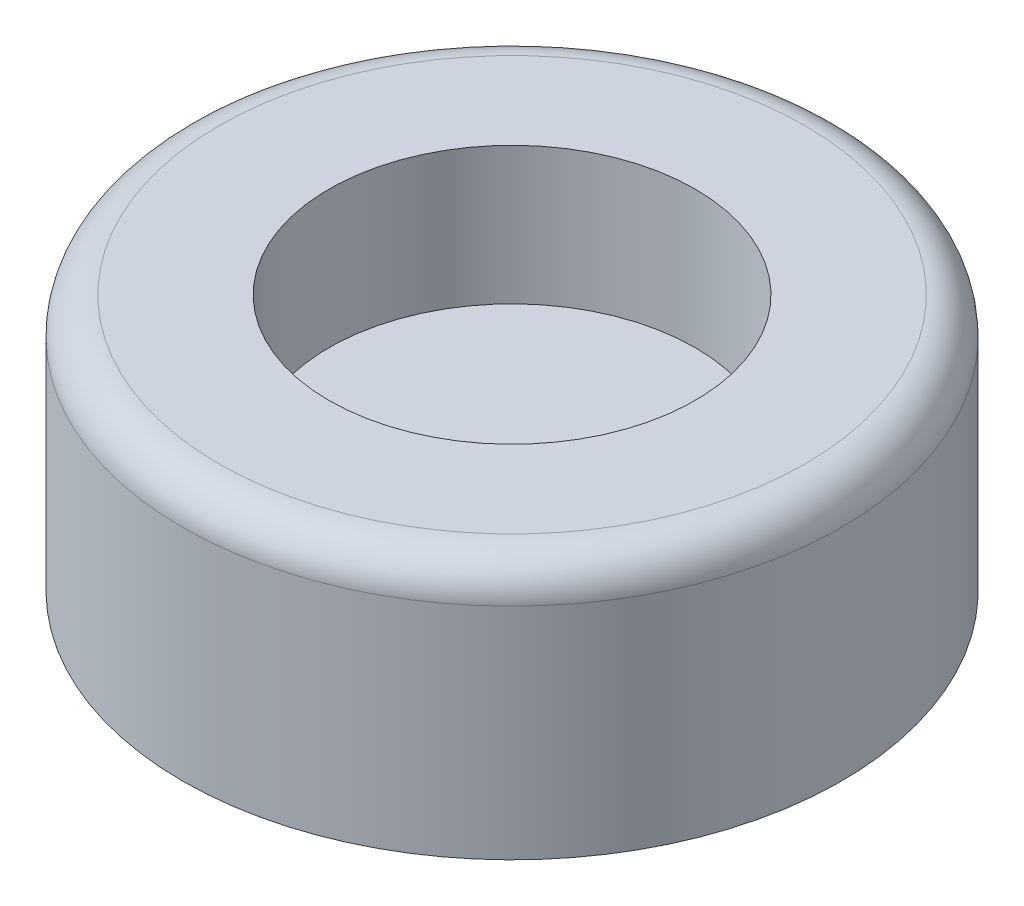
SolidWorks part; units mm, degrees
ref_plane "Front Plane" through (0, 0, 0) normal (0, 0, 1) x (1, 0, 0)
ref_plane "Top Plane" through (0, 0, 0) normal (0, 1, 0) x (1, 0, 0)
ref_plane "Right Plane" through (0, 0, 0) normal (1, 0, 0) x (0, 0, -1)
sketch "Sketch1" plane through (0, 0, 0) normal (0, 1, 0) x (1, 0, 0)
  circle A0 centre (0, 0) radius 11.43
extrude "Boss-Extrude1" add sketch "Sketch1" along normal blind 8.89
sketch "Sketch2" plane through (0, 8.89, 0) normal (0, 1, 0) x (1, 0, 0)
  circle A0 centre (0, 0) radius 6.35
extrude "Cut-Extrude1" cut sketch "Sketch2" against normal blind 4.7625
sketch "Sketch3" plane through (0, 0, 0) normal (0, -1, 0) x (1, 0, 0)
  circle A0 centre (0, 0) radius 3.175
fillet "Fillet4" radius 1.27 1 edges at (0, 8.89, 11.43)
sketch "Sketch4" plane through (0, 8.89, 0) normal (0, 1, 0) x (1, 0, 0)
  line L0 (0, 0) -> (0, 10.16) construction
  circle A0 centre (0, 0) radius 10.16 construction
  circle A1 centre (0, 0) radius 11.938 construction
  circle A2 centre (0, 11.938) radius 1.5875
ref_axis "Axis1" through (0, 4.1275, 0) along (0, 1, 0)
extrude "Cut-Extrude2" cut sketch "Sketch3" against normal blind 2.54
